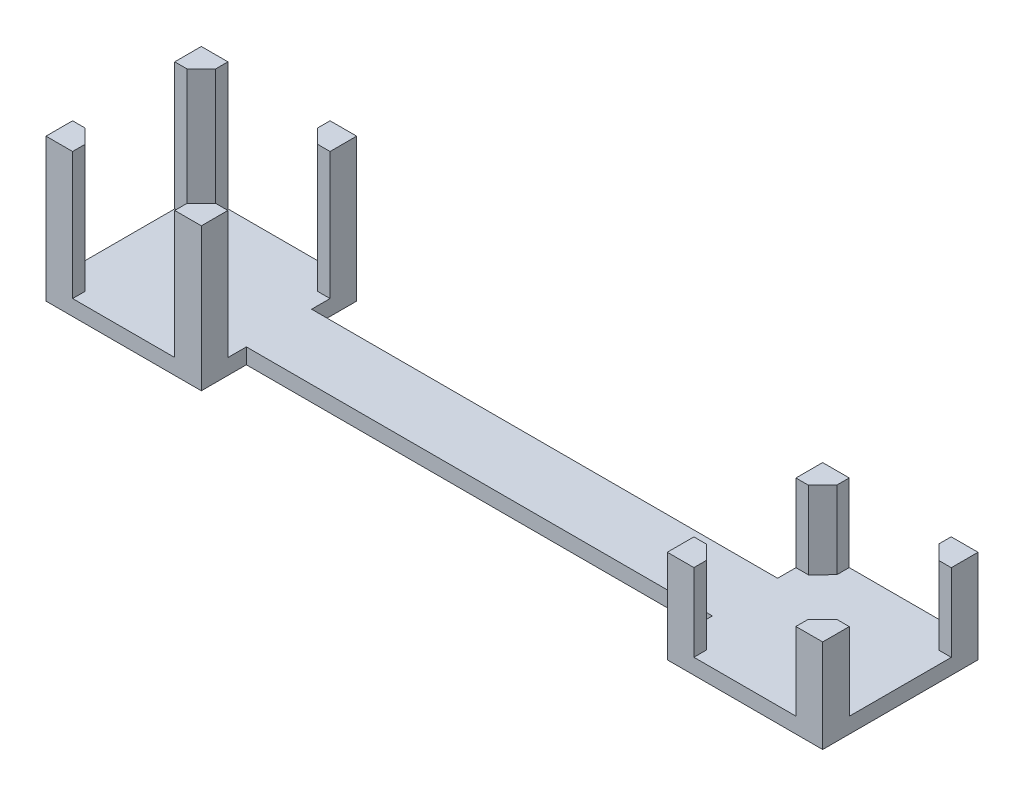
SolidWorks part; units mm, degrees
ref_plane "Front Plane" through (0, 0, 0) normal (0, 0, 1) x (1, 0, 0)
ref_plane "Top Plane" through (0, 0, 0) normal (0, 1, 0) x (1, 0, 0)
ref_plane "Right Plane" through (0, 0, 0) normal (1, 0, 0) x (0, 0, -1)
sketch "Base_sch" plane through (0, 0, 0) normal (0, 1, 0) x (1, 0, 0)
  line L5 (25, 10.5) -> (25, 25)
  line L6 (25, -25) -> (-25, -25)
  line L7 (25, 10.5) -> (175, 10.5)
  line L8 (25, -10.5) -> (175, -10.5)
  line L15 (25, -25) -> (25, -10.5)
  line L16 (25, 25) -> (-25, 25)
  line L25 (-25, -25) -> (-25, 25)
  line L28 (225.0138, -25) -> (175, -25)
  line L29 (225.0138, -25) -> (225.0138, 25)
  line L30 (225.0138, 25) -> (175, 25)
  line L31 (175, -25) -> (175, -10.5)
  line L36 (175, 10.5) -> (175, 25)
  point P0 (0, 0)
  point P1 (0, 0)
  point P8 (299.9942, 0)
  dimension "D1" = 50
  dimension "D2" = 50
  dimension "D3" = 50.0138
  dimension "D4" = 50
  dimension "D5" = 150
extrude "base_extr" add sketch "Base_sch" along normal blind 5
sketch "motor_support_sch" plane through (0, 5, 0) normal (0, 1, 0) x (1, 0, 0)
  line L0 (25, 10.5) -> (25, 25) construction
  line L5 (-25, 16.4394) -> (-25, 25)
  line L6 (-25, 25) -> (-16.4394, 25)
  line L13 (16.4394, 25) -> (25, 25)
  line L14 (25, 25) -> (25, 16.4394)
  line L15 (25, -16.4394) -> (25, -25)
  line L16 (25, -25) -> (16.4394, -25)
  line L17 (-18.7197, 18.7197) -> (-21, 16.4394)
  line L18 (-18.7197, 18.7197) -> (-16.4394, 21)
  line L19 (18.7197, 18.7197) -> (16.4394, 21)
  line L20 (18.7197, 18.7197) -> (21, 16.4394)
  line L21 (-18.7197, -18.7197) -> (-21, -16.4394)
  line L22 (-18.7197, -18.7197) -> (-16.4394, -21)
  line L23 (18.7197, -18.7197) -> (16.4394, -21)
  line L24 (18.7197, -18.7197) -> (21, -16.4394)
  line L25 (-21, 16.4394) -> (-25, 16.4394)
  line L26 (-25, 25) -> (-25, -25) construction
  line L27 (-16.4394, 21) -> (-16.4394, 25)
  line L28 (25, 25) -> (-25, 25) construction
  line L29 (16.4394, 21) -> (16.4394, 25)
  line L30 (21, 16.4394) -> (25, 16.4394)
  line L31 (-21, -16.4394) -> (-25, -16.4394)
  line L32 (-16.4394, -21) -> (-16.4394, -25)
  line L33 (-25, -25) -> (25, -25) construction
  line L34 (16.4394, -21) -> (16.4394, -25)
  line L35 (21, -16.4394) -> (25, -16.4394)
  line L36 (25, -25) -> (25, -10.5) construction
  line L37 (-25, -16.4394) -> (-25, -25)
  line L38 (-25, -25) -> (-16.4394, -25)
  point P0 (0, 0)
  point P10 (299.9942, 0)
  dimension "D7" = 41.4394
  dimension "D8" = 41.4394
extrude "Motor_1_extr" add sketch "motor_support_sch" along normal blind 41
sketch "shaft_motor_support_sch" plane through (0, 5, 0) normal (0, 1, 0) x (1, 0, 0)
  line L10 (181.2803, -18.7197) -> (179, -16.4394)
  line L11 (181.2803, -18.7197) -> (183.5606, -21)
  line L18 (179, -16.4394) -> (175, -16.4394)
  line L19 (183.5606, -21) -> (183.5606, -25)
  line L22 (175, -16.4394) -> (175, -25)
  line L23 (175, -25) -> (183.5606, -25)
  line L24 (175, 25) -> (175, 16.4025)
  line L25 (175, -24.6047) -> (175, -25)
  line L26 (175, 25) -> (175, 10.5) construction
  line L27 (175, 25) -> (183.5606, 25)
  line L28 (225.0138, -25) -> (225.0138, -16.4394)
  line L29 (225.0138, 25) -> (175, 25) construction
  line L30 (175, -10.5) -> (175, -25) construction
  line L31 (175, -25) -> (225.0138, -25) construction
  line L32 (175, 16.4025) -> (179, 16.4025)
  line L33 (183.5606, 25) -> (183.5606, 21.024)
  line L34 (183.5606, 21.024) -> (179, 16.4025)
  line L35 (225.0138, 25) -> (216.3857, 25)
  line L36 (225.0138, 25) -> (225.0138, 16.4025)
  line L37 (225.0138, -25) -> (225.0138, 25) construction
  line L38 (225.0138, 16.4025) -> (221.0566, 16.4025)
  line L39 (216.3857, 25) -> (216.3857, 21.024)
  line L40 (216.3857, 21.024) -> (221.0566, 16.4025)
  line L41 (225.0138, -25) -> (216.3857, -25)
  line L42 (216.3857, -25) -> (216.3857, -21)
  line L43 (225.0138, -16.4394) -> (221.0566, -16.4394)
  line L44 (221.0566, -16.4394) -> (216.3857, -21)
  point P0 (175, 7.9008)
  point P6 (620.659, -6.4152)
  line M11 (175, -25) -> (225.0138, -25)
  line M13 (225.0138, 25) -> (175, 25)
  dimension "D9" = 0
  dimension "D10" = 8.5606
  dimension "D11" = 4
  dimension "D12" = 3.2248
  dimension "D13" = 4
  dimension "D14" = 8.5606
  dimension "D15" = 0
extrude "shaft_motor_support_extr" add sketch "shaft_motor_support_sch" along normal blind 25 contours M13 | L18 L22 L19 L11 L10 M11 | M11 | L33 M13 region at (178.8239, 5, 21.1761) region at (221.1644, 5, 21.1848) region at (178.819, 5, -21.1622) region at (221.1693, 5, -21.1709)
